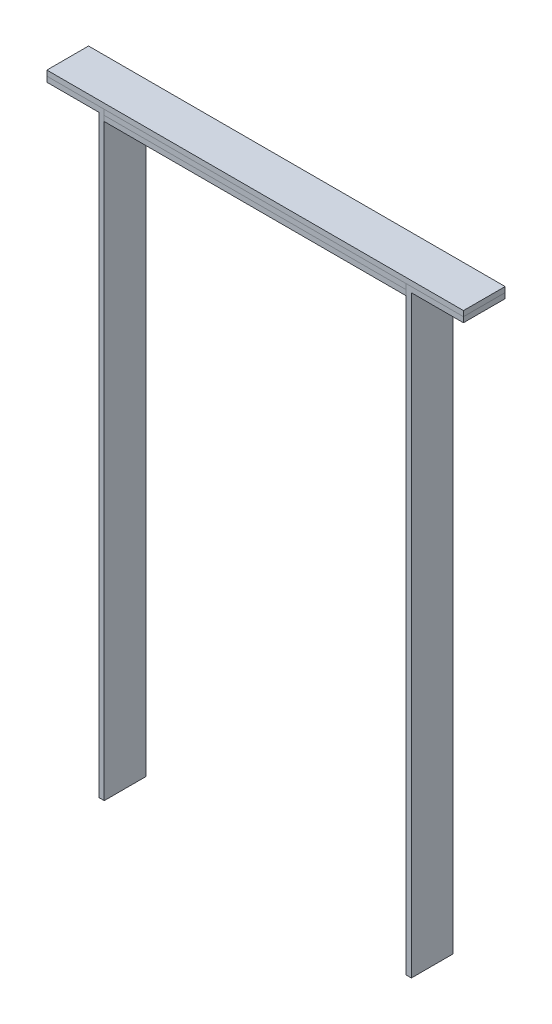
SolidWorks part; units mm, degrees
ref_plane "Front Plane" through (0, 0, 0) normal (0, 0, 1) x (1, 0, 0)
ref_plane "Top Plane" through (0, 0, 0) normal (0, 1, 0) x (1, 0, 0)
ref_plane "Right Plane" through (0, 0, 0) normal (1, 0, 0) x (0, 0, -1)
sketch "Sketch2" plane through (0, 0, 0) normal (0, 0, 1) x (1, 0, 0)
  line L0 (0, 0) -> (0, 142.46)
  line L1 (0, 142.46) -> (-12.5, 142.46)
  line L2 (-12.5, 142.46) -> (-12.5, 143.73)
  line L3 (-12.5, 143.73) -> (1.27, 143.73)
  line L4 (1.27, 143.73) -> (1.27, 0)
  line L5 (1.27, 0) -> (0, 0)
  line L6 (-12.5, 143.73) -> (-12.5, 145)
  line L7 (-12.5, 145) -> (87.5, 145)
  line L8 (87.5, 145) -> (87.5, 143.73)
  line L9 (87.5, 143.73) -> (-12.5, 143.73)
  line L10 (87.5, 143.73) -> (87.5, 142.46)
  line L11 (87.5, 142.46) -> (75, 142.46)
  line L12 (75, 142.46) -> (75, 0)
  line L13 (75, 0) -> (73.73, 0)
  line L14 (73.73, 0) -> (73.73, 143.73)
  line L15 (73.73, 143.73) -> (87.5, 143.73)
  line L17 (1.27, 143.73) -> (73.73, 143.73)
  line L18 (1.27, 143.73) -> (1.27, 142.46)
  line L19 (1.27, 142.46) -> (73.73, 142.46)
  line L20 (73.73, 143.73) -> (73.73, 142.46)
  line L21 (1.27, 142.46) -> (73.73, 142.46)
  line L22 (1.27, 142.46) -> (1.27, 141.19)
  line L23 (1.27, 141.19) -> (73.73, 141.19)
  line L24 (73.73, 142.46) -> (73.73, 141.19)
  dimension "D1" = 1.27
  dimension "D2" = 1.27
  dimension "D3" = 100
  dimension "D4" = 12.5
  dimension "D5" = 145
  dimension "D6" = 1.27
extrude "Boss-Extrude1" add sketch "Sketch2" along normal blind 10 contours L5 L4 L3 L2 L1 L0 | L14 L13 L12 L11 L10 L9 region at (0.0841, 77.5641, 0) region at (74.9159, 77.5641, 0)
extrude "Boss-Extrude2" add sketch "Sketch2<4>" along normal blind 10 separate body contours L4 L19 L14 L9 region at (37.5, 143.095, 0)
sketch "Sketch2<4>" plane through (0, 0, 0) normal (0, 0, 1) x (1, 0, 0) same geometry as "Sketch2"
extrude "Boss-Extrude3" add sketch "Sketch2<5>" along normal blind 10 separate body contours L9 L8 L7 L6 L3 region at (37.5, 144.365, 0)
sketch "Sketch2<5>" plane through (0, 0, 0) normal (0, 0, 1) x (1, 0, 0) same geometry as "Sketch2"
extrude "Boss-Extrude4" add sketch "Sketch2<7>" along normal blind 10 separate body contours L4 L23 L14 L19 region at (37.5, 141.825, 0)
sketch "Sketch2<7>" plane through (0, 0, 0) normal (0, 0, 1) x (1, 0, 0) same geometry as "Sketch2"
